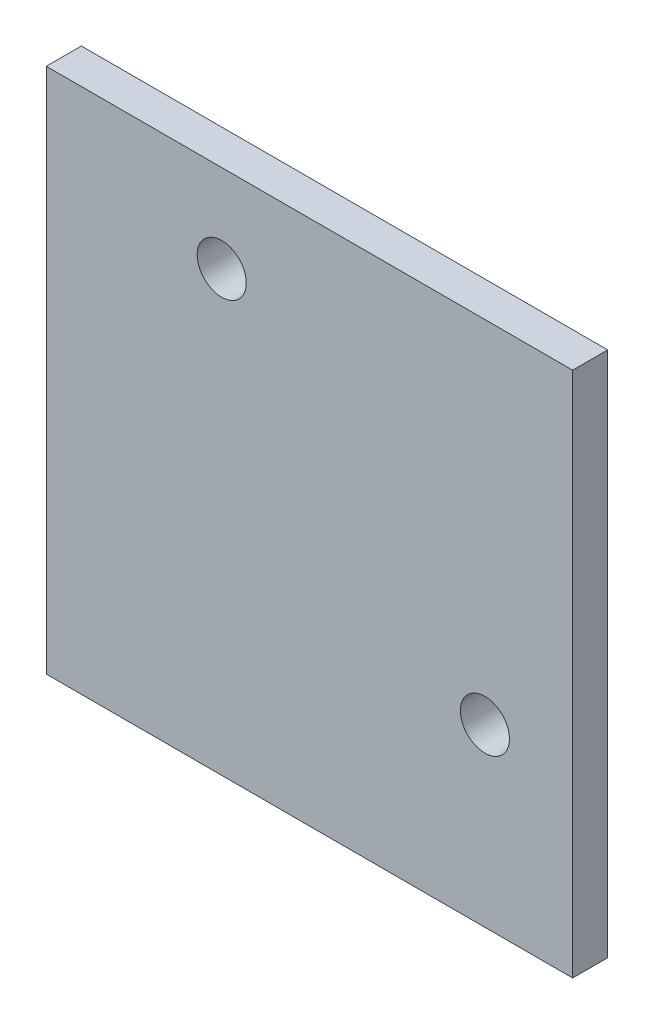
SolidWorks part; units mm, degrees
material "Простая углеродистая сталь"
ref_plane "Спереди" through (0, 0, 0) normal (0, 0, 1) x (1, 0, 0)
ref_plane "Сверху" through (0, 0, 0) normal (0, 1, 0) x (1, 0, 0)
ref_plane "Справа" through (0, 0, 0) normal (1, 0, 0) x (0, 0, -1)
sketch "Эскиз1" plane through (0, 0, 0) normal (0, 0, 1) x (1, 0, 0)
  line L1 (0, 0) -> (150, 0)
  line L2 (0, 0) -> (0, -150)
  line L3 (0, -150) -> (150, -150)
  line L4 (150, 0) -> (150, -150)
  line L5 (75, -150) -> (75, 0) construction
  line L6 (0, -75) -> (150, -75) construction
  point P192 (75, -75)
  dimension "D1" = 150
  dimension "D2" = 150
base flange "Базовая кромка1" sketch "Эскиз1" thickness 10 reverse thickness direction no parameters "D1"=0.8
sketch "Эскиз2" plane through (0, 0, -10) normal (0, 0, -1) x (-1, 0, 0)
  circle A0 centre (-63.2969, -37.2697) radius 7
  dimension "D1" = 14
sketch "Эскиз3" plane through (0, 0, -10) normal (0, 0, -1) x (-1, 0, 0)
  line L0 (-150, -150) -> (-150, 0) construction
  line L1 (0, -150) -> (-150, -150) construction
  line L2 (-150, 0) -> (0, 0) construction
  line L3 (-75, -150) -> (-100, -120.6294) construction
  circle A0 centre (-125, -100) radius 7
  circle A1 centre (-50, -25) radius 7
  dimension "D1" = 14
  dimension "D2" = 25
  dimension "D3" = 50
  dimension "D4" = 25
  dimension "D5" = 100
extrude "Вырез-Вытянуть1" cut sketch "Эскиз3" against normal blind 10 normal cut yes
sketch "Сгиб-Линии1" [suppressed] plane through (0, 0, 0) normal (0, 1, 0) x (1, 0, 0)
sketch "Граничная рамка1" [suppressed] plane through (0, 0, 0) normal (0, 1, 0) x (1, 0, 0)
sheet metal parameters "Листовой металл1" thickness 10 parameters "D1"=0.8
flat pattern "Развертка1" [suppressed]
sketch "Сгиб-Линии2" plane through (0, 0, 0) normal (0, 1, 0) x (1, 0, 0)
sketch "Граничная рамка2" [suppressed] plane through (0, 0, 0) normal (0, 1, 0) x (1, 0, 0)
sheet metal parameters "Листовой металл2" thickness 10 parameters "D1"=0.8
flat pattern "Развертка1" [suppressed]
sketch "Сгиб-Линии2" plane through (0, 0, 0) normal (0, 1, 0) x (1, 0, 0)
sketch3d "Граничная рамка2" [suppressed]
  line L0 (0, -150, 0) -> (150, -150, 0) construction
  line L1 (0, 0, 0) -> (150, 0, 0) construction
  line L2 (0, -150, 0) -> (0, 0, 0) construction
  line L3 (150, -150, 0) -> (150, 0, 0) construction
sketch "Эскиз2-1" [suppressed] plane through (0, 0, -10) normal (0, 0, -1) x (-1, 0, 0)
  circle A0 centre (-63.2969, -37.2697) radius 7
  dimension "D1" = 14
